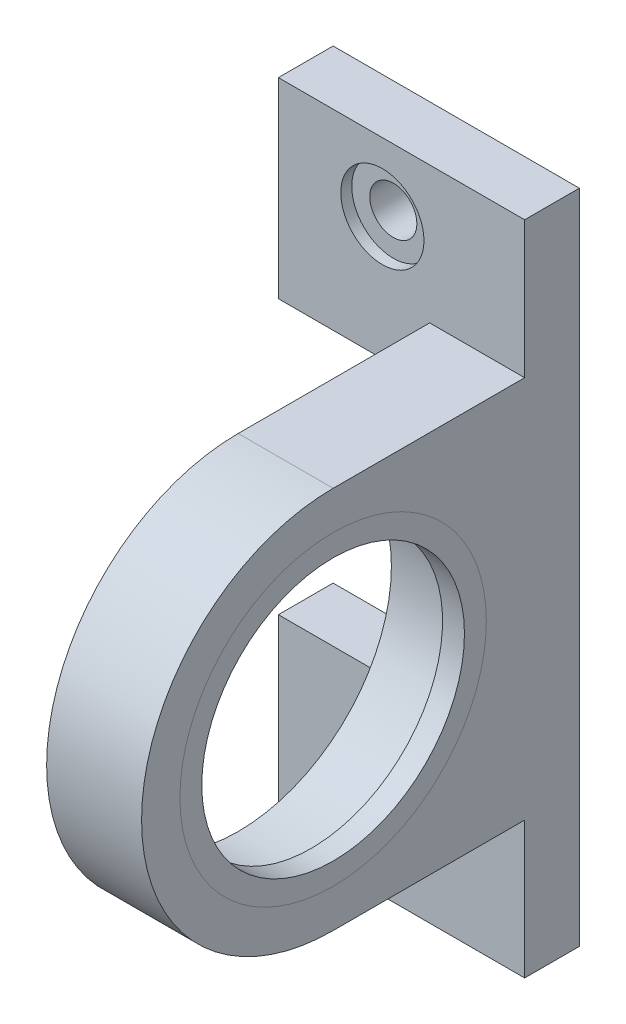
SolidWorks part; units mm, degrees
ref_plane "前视基准面" through (0, 0, 0) normal (0, 0, 1) x (1, 0, 0)
ref_plane "上视基准面" through (0, 0, 0) normal (0, 1, 0) x (1, 0, 0)
ref_plane "右视基准面" through (0, 0, 0) normal (1, 0, 0) x (0, 0, -1)
sketch "草图2" plane through (0, 0, 0) normal (0, 0, 1) x (1, 0, 0)
  line L0 (-14.7736, 24.3382) -> (-14.7736, -35.6618)
  line L1 (-14.7736, -35.6618) -> (30.2264, -35.6618)
  line L2 (7.7264, -35.6618) -> (7.7264, -18.1618)
  line L3 (21.55, -18.1618) -> (-6.0971, -18.1618)
  line L4 (-6.0971, -18.1618) -> (-6.0971, 6.8382)
  line L5 (-6.0971, 6.8382) -> (21.55, 6.8382)
  line L6 (7.7264, 6.8382) -> (7.7264, 24.3382)
  line L7 (30.2264, 24.3382) -> (-14.7736, 24.3382)
  line L8 (7.7264, 28.8603) -> (7.7264, -39.8897) construction
  line L9 (21.55, -18.1618) -> (21.55, 6.8382)
  line L10 (30.2264, 24.3382) -> (30.2264, -35.6618)
  line L11 (-18.1559, -5.6618) -> (33.2411, -5.6618) construction
  line L12 (44.0218, -5.6618) -> (44.0218, 26.2521) construction
  point P16 (-6.0971, -5.6618)
  point P17 (-14.7736, -5.6618)
  dimension "D1" = 45
  dimension "D2" = 25
  dimension "D3" = 60
extrude "凸台-拉伸2" add sketch "草图2" along normal blind 5 contours L6 L7 L0 L1 L2 L3 L4 L5 | L10 L7 L6 L5 L9 L3 L2 L1 region at (-3.5236, 23.6974, 0) region at (18.9764, 23.6974, 0)
sketch "草图4" plane through (0, 0, 5) normal (0, 0, 1) x (1, 0, 0)
  line L0 (-18.165, -5.6618) -> (33.9165, -5.6618) construction
  line L1 (-14.7736, 24.3382) -> (-14.7736, -35.6618) construction
  line L2 (-14.7736, -23.1618) -> (-6.0971, -23.1618)
  line L3 (-14.7736, -23.1618) -> (-14.7736, 11.8382)
  line L4 (-14.7736, 11.8382) -> (-6.0971, 11.8382)
  line L5 (-6.0971, -23.1618) -> (-6.0971, 11.8382)
  line L6 (-6.0971, -18.1618) -> (-6.0971, 6.8382) construction
  line L7 (7.7264, -39.813) -> (7.7264, 28.1228) construction
  line L8 (30.2264, 11.8382) -> (21.55, 11.8382)
  line L9 (21.55, -23.1618) -> (21.55, 11.8382)
  line L10 (30.2264, -23.1618) -> (21.55, -23.1618)
  line L11 (30.2264, -23.1618) -> (30.2264, 11.8382)
  point P17 (-14.7736, -5.6618)
  dimension "D1" = 35
extrude "凸台-拉伸15" add sketch "草图4" along normal blind 35
sketch "草图5" plane through (-14.7736, 0, 0) normal (-1, 0, 0) x (0, 0, 1)
  line L0 (0, -5.6618) -> (40, -5.6618)
  line L1 (0, 24.3382) -> (0, -35.6618) construction
  line L2 (40, 11.8382) -> (40, -23.1618) construction
  line L3 (22.5, 11.8382) -> (40, 11.8382)
  line L4 (40, 11.8382) -> (40, -23.1618)
  line L5 (40, -23.1618) -> (22.5, -23.1618)
  circle A0 centre (22.5, -5.6618) radius 17.5
  line M5 (5, -23.1618) -> (40, -23.1618)
  line M6 (40, -23.1618) -> (40, 11.8382)
  line M7 (40, 11.8382) -> (5, 11.8382)
  dimension "D1" = 35
extrude "切除-拉伸1" cut sketch "草图5" against normal blind 45 contours A0 M5 M6 | A0 M6 M7 region at (-14.7736, 7.9293, 36.0911) region at (-14.7736, -19.2528, 36.0911)
sketch "草图6" plane through (-14.7736, 0, 0) normal (-1, 0, 0) x (0, 0, 1)
  circle A0 centre (22.5, -5.6618) radius 14
  dimension "D1" = 28
extrude "切除-拉伸2" cut sketch "草图6" against normal blind 45
fillet "圆角1" radius 5 4 edges at (-6.0971, 6.8382, 2.5) (21.55, 6.8382, 2.5) (-6.0971, -18.1618, 2.5) (21.55, -18.1618, 2.5)
sketch "草图7" plane through (-6.0971, 0, 0) normal (1, 0, 0) x (0, 0, -1)
  circle A0 centre (-22.5, -5.6618) radius 15
  circle A1 centre (-22.5, -5.6618) radius 13
extrude "凸台-拉伸16" add sketch "草图7" against normal blind 1
sketch "草图8" plane through (21.55, 0, 0) normal (-1, 0, 0) x (0, 0, 1)
  circle A0 centre (22.5, -5.6618) radius 15
  circle A1 centre (22.5, -5.6618) radius 10
sketch "草图9" plane through (0, 0, 5) normal (0, 0, 1) x (1, 0, 0)
  line L0 (7.7264, 24.3382) -> (7.7264, -35.6618)
  line L13 (30.2264, 24.3382) -> (-14.7736, 24.3382) construction
  line L14 (-14.7736, -35.6618) -> (30.2264, -35.6618) construction
sketch "草图11" plane through (0, 0, 5) normal (0, 0, 1) x (1, 0, 0)
  line L0 (-14.7736, 18.0882) -> (30.2264, 18.0882)
  line L1 (-14.7736, 24.3382) -> (-14.7736, 11.8382) construction
  line L2 (30.2264, 24.3382) -> (30.2264, 11.8382) construction
  line L3 (7.7264, 24.3382) -> (7.7264, -35.6618) construction
  line L4 (30.2264, 24.3382) -> (-14.7736, 24.3382) construction
  line L5 (-14.7736, -35.6618) -> (30.2264, -35.6618) construction
  line L6 (7.7264, -5.6618) -> (45.6912, -5.6618) construction
  line L10 (-14.7736, -29.4118) -> (30.2264, -29.4118)
  line L11 (-14.7736, -23.1618) -> (-14.7736, -35.6618) construction
  point P4 (-1.7736, 18.0882)
  point P16 (-1.7736, -29.4118)
  point P18 (17.2264, -29.4118)
  point P25 (17.2264, 18.0882)
  dimension "D1" = 13
split "分割1" trim tools "草图9" bodies to split 111 resulting bodies 117 118
delete or keep bodies "实体-删除/保留 2" type delete bodies bodies 117
hole_wizard "打孔尺寸(%根据六角头螺)栓 全螺纹的类型1" positions "3D草图2" profile "草图13" counterbore size "M4" standard "GB"
sketch3d "3D草图2"
  point P0 (17.2264, 18.0882, 5)
  point P3 (17.2264, -29.4118, 5)
sketch "草图13" plane through (17.2264, 18.0882, 5) normal (1, 0, 0) x (0, -1, 0)
  line L0 (0, 0) -> (0, 6.2919)
  line L1 (0, 6.2919) -> (2.15, 5)
  line L2 (2.15, 5) -> (2.15, 1)
  line L3 (2.15, 1) -> (3.8, 1)
  line L4 (3.8, 1) -> (3.8, 0)
  line L5 (3.8, 0) -> (0, 0)
  line L10 (0, 6.2919) -> (-2.15, 5) construction
  line L11 (0, -6.35) -> (0, 107.95) construction
  dimension "孔直径" = 4.3
  dimension "孔深度" = 5
  dimension "柱形沉头孔直径" = 7.6
  dimension "柱形沉头孔深度" = 1
  dimension "导头角度" = 118
ref_plane "基准面1" through (30.2264, 0, 0) normal (1, 0, 0) x (0, 0, -1)
sketch "草图14" plane through (30.2264, 0, 0) normal (1, 0, 0) x (0, 0, -1)
  circle A2 centre (-22.5, -5.6618) radius 14
extrude "凸台-拉伸18" add sketch "草图14" against normal blind 2 separate body
sketch "草图15" plane through (28.2264, 0, 0) normal (-1, 0, 0) x (0, 0, 1)
  circle A0 centre (22.5, -5.6618) radius 12
extrude "切除-拉伸3" cut sketch "草图15" against normal blind 3
